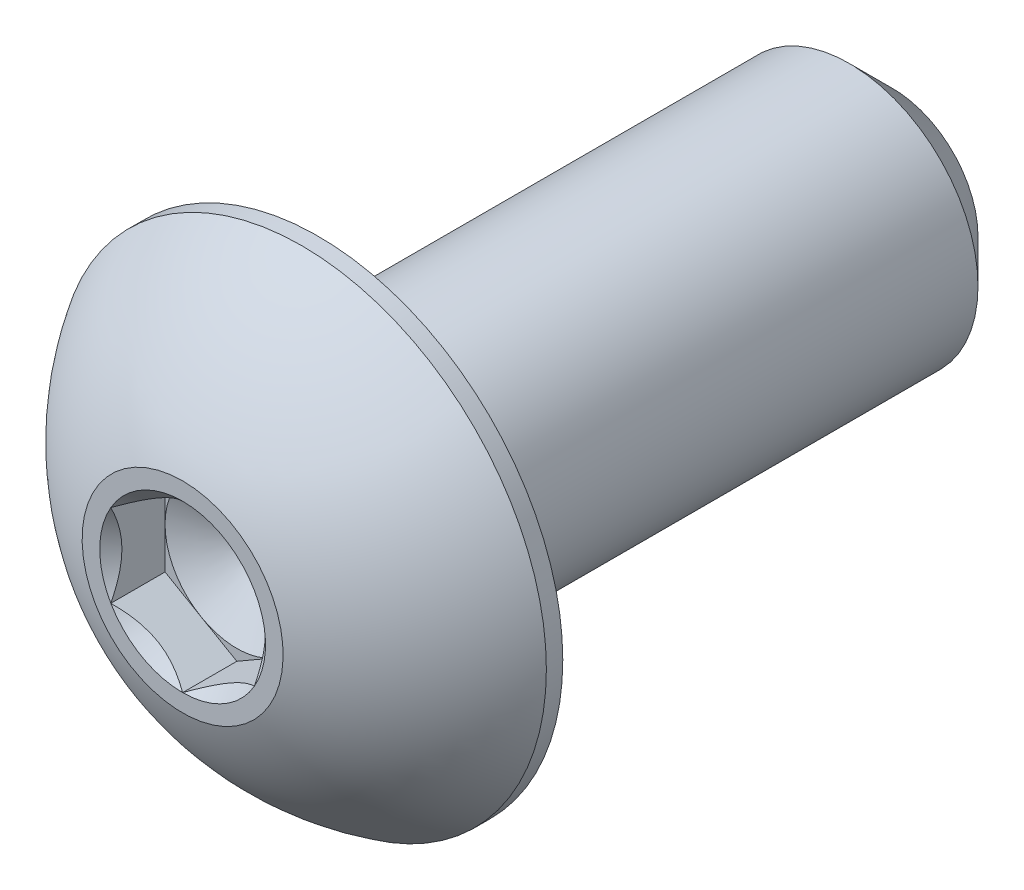
SolidWorks part; units mm, degrees
ref_plane "Front Plane" through (0, 0, 0) normal (0, 0, 1) x (1, 0, 0)
ref_plane "Top Plane" through (0, 0, 0) normal (0, 1, 0) x (1, 0, 0)
ref_plane "Right Plane" through (0, 0, 0) normal (1, 0, 0) x (0, 0, -1)
sketch "Sketch1" plane through (0, 0, 0) normal (1, 0, 0) x (0, 0, -1)
  line L0 (-3.9243, 0) -> (3.9243, 0) construction
  line L1 (-2.4257, 2.7051) -> (-2.4257, -2.7051) construction
  line L2 (-3.9243, 0.7937) -> (-3.9243, -0.7937) construction
  line L3 (3.9243, 1.4224) -> (3.9243, -1.4224) construction
  line L4 (3.8846, 1.4911) -> (4.2021, 0.9412) construction
  line L5 (4.2021, 0.9412) -> (4.5196, 1.4911) construction
  line L6 (4.5196, 1.4911) -> (3.8846, 1.4911) construction
  line L7 (4.2021, 1.4911) -> (4.2021, 1.4224) construction
  line L8 (4.2021, 0.9412) -> (4.2021, 1.01) construction
  line L9 (4.1624, 1.01) -> (4.2418, 1.01)
  line L10 (-3.9243, 1.1113) -> (-3.9243, -1.1113) construction
  line L11 (-2.4257, 2.7051) -> (-2.6071, 2.7051) construction
  line L12 (-3.9243, 0.7937) -> (-3.3249, 0.7937) construction
  line L13 (-3.3249, 0.7937) -> (-2.8666, 0) construction
  point P5 (-2.4257, 0)
  point P10 (1.7018, -1.4224)
  dimension "Drive Size" = 1.5875
  dimension "Head Diameter" = 5.4102
  dimension "Head Height" = 1.4986
  dimension "Screw Size Decimal Equivalent" = 2.8448
  dimension "Length" = 6.35
  dimension "D1" = 2.2225
  dimension "Pitch" = 0.635
  dimension "D2" = 0.0794
  dimension "D3" = 2.2225
  dimension "D4" = 0.1814
  dimension "D5" = 60
  dimension "D6" = 0.5994
sketch "Sketch2" plane through (0, 0, 0) normal (1, 0, 0) x (0, 0, -1)
  line L0 (-3.9243, 0.7937) -> (-3.9243, 1.1113)
  line L1 (-2.6071, 2.7051) -> (-2.4257, 2.7051)
  line L2 (-2.4257, 2.7051) -> (-2.4257, 1.4224)
  line L3 (-2.4257, 2.7051) -> (-2.4257, -2.7051) construction
  line L4 (-2.4257, 1.4224) -> (3.4481, 1.4224)
  line L5 (3.9243, 0.9462) -> (3.9243, 0)
  line L6 (-3.9243, 0.7937) -> (-3.3249, 0.7937)
  line L7 (-3.3249, 0.7937) -> (-2.8666, 0)
  line L8 (3.9243, 0) -> (-2.8666, 0)
  line L9 (3.4481, 1.4224) -> (3.9243, 0.9462)
  line L10 (3.4481, -1.4224) -> (3.4481, 1.4224) construction
  arc A0 (-2.6071, 2.7051) -> (-3.9243, 1.1113) centre (-0.9567, 0) ccw
  point P13 (3.9243, 1.4224)
  point P25 (3.4481, 0)
  dimension "D1" = 0.4763
  dimension "D2" = 45
revolve "Revolve1" add sketch "Sketch2" angle 360 about L0
sketch "Sketch3" plane through (0, 0, 0) normal (0, 0, 1) x (1, 0, 0)
  line L1 (0, 0.9165) -> (-0.7937, 0.4583)
  line L2 (-0.7937, 0.4583) -> (-0.7937, -0.4583)
  line L3 (-0.7937, -0.4583) -> (0, -0.9165)
  line L4 (0, -0.9165) -> (0.7938, -0.4583)
  line L5 (0.7938, -0.4583) -> (0.7937, 0.4583)
  line L6 (0.7937, 0.4583) -> (0, 0.9165)
  circle A0 centre (0, 0) radius 0.7937 construction
extrude "Cut-Extrude1" cut sketch "Sketch3" along normal through all from vertex starting at point (0, 0.7937, 3.3249)
sketch "Sketch4" plane through (0, 0, 3.9243) normal (0, 0, 1) x (1, 0, 0)
  circle A0 centre (0, 0) radius 0.9165
extrude "Cut-Extrude2" cut sketch "Sketch4" against normal up to next (1.0577 mm away) draft 45
sketch "Sketch9" plane through (0, 0, 0) normal (1, 0, 0) x (0, 0, -1)
  line L0 (3.9243, -1.4224) -> (-2.4257, -1.4224) construction
  line L1 (-2.4257, -1.4224) -> (3.4481, -1.4224) construction
  line L2 (3.9243, -0.9462) -> (3.9243, 0.9462) construction
  line L3 (-2.4257, -1.4224) -> (-2.4257, 1.4224) construction
  point P9 (2.9718, -1.4224)
  dimension "D1" = 0.9525
sketch "Sketch5" [suppressed] plane through (0, 0, -3.9243) normal (0, 0, -1) x (-1, 0, 0)
  circle A0 centre (0, 0) radius 1.4224
ref_axis "Center Axis1" [suppressed] through (0, 0, -7.843) along (0, 0, 1)
ref_plane "Contact Plane1" [suppressed] through (0, 0, -3.9243) normal (0, 0, 1) x (1, 0, 0)
ref_plane "Contact Plane2" [suppressed] through (0, 0, 2.4257) normal (0, 0, 1) x (1, 0, 0)
curve "Helix/Spiral1" [suppressed] pitch 0.635 height 6.985 turns 11
sketch "Sketch6" [suppressed] plane through (0, 0, 0) normal (1, 0, 0) x (0, 0, -1)
  line L0 (3.9243, 1.4224) -> (4.4799, 1.4224)
  line L1 (4.4799, 1.4224) -> (4.2418, 1.01)
  line L2 (4.1624, 1.01) -> (4.2418, 1.01)
  line L3 (4.1624, 1.01) -> (3.9243, 1.4224)
  line L4 (4.2021, 0.9412) -> (4.5196, 1.4911) construction
sweep "Cut-Sweep1" [suppressed] cut profiles "Sketch6" path "Helix/Spiral1"
sketch "Sketch7" [suppressed] plane through (0, 0, 0) normal (1, 0, 0) x (0, 0, -1)
  line L0 (-3.3249, 1.4224) -> (-2.4257, 1.4224)
  line L1 (-3.3249, 1.4224) -> (-3.3249, 0.7937)
  line L2 (-3.3249, 0.7937) -> (-2.8666, 0)
  line L3 (-2.8666, 0) -> (-1.1037, 0)
  line L5 (-2.4257, 2.7051) -> (-2.4257, -2.7051) construction
  line L6 (-2.4257, 1.4224) -> (-1.1037, 0.9412)
  line L7 (-1.1037, 0.9412) -> (-1.1037, 0)
  dimension "D1" = 20
revolve "Revolve2" [suppressed] add sketch "Sketch7" angle 360 about L0
equation "\"D2@Sketch1\"=\"Pitch@Sketch1\"*.125"
equation "\"D1@Sketch1\"=\"Pitch@Sketch1\"*3.5"
equation "\"D3@Sketch1\"=\"Drive Size@Sketch1\"*1.4"
equation "\"D4@Sketch1\"=(\"D3@Sketch1\"-\"Drive Size@Sketch1\")/3.5"
equation "\"D6@Sketch1\"=\"Head Height@Sketch1\"*.40"
equation "\"D1@Sketch2\"=\"Pitch@Sketch1\"*.750"
equation "\"D4@Helix/Spiral1\"=\"Pitch@Sketch1\""
equation "\"D3@Helix/Spiral1\" = \"D4@Helix/Spiral1\" + \"Length@Sketch1\""
equation "\"D1@Sketch9\"=\"Pitch@Sketch1\"*1.5"
